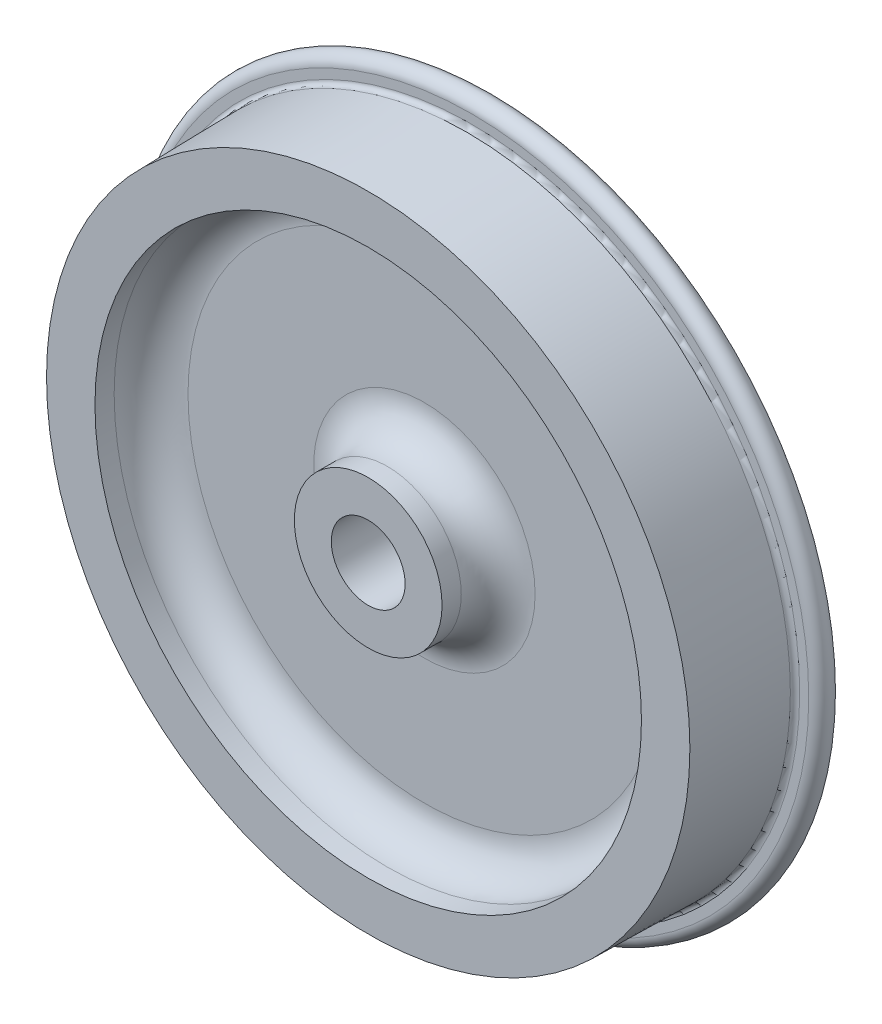
SolidWorks part; units mm, degrees
material "Gray Cast Iron"
ref_plane "Front Plane" through (0, 0, 0) normal (0, 0, 1) x (1, 0, 0)
ref_plane "Top Plane" through (0, 0, 0) normal (0, 1, 0) x (1, 0, 0)
ref_plane "Right Plane" through (0, 0, 0) normal (1, 0, 0) x (0, 0, -1)
sketch "Sketch1" plane through (0, 0, 0) normal (0, 0, 1) x (1, 0, 0)
  circle A0 centre (0, 0) radius 58.42
  dimension "D1" = 116.84
extrude "Boss-Extrude1" add sketch "Sketch1" along normal blind 13.97
sketch "Sketch2" plane through (0, 0, 13.97) normal (0, 0, 1) x (1, 0, 0)
  circle A0 centre (0, 0) radius 12.7
  circle A1 centre (0, 0) radius 46.99
  dimension "D1" = 25.4
  dimension "D2" = 93.98
extrude "Cut-Extrude1" cut sketch "Sketch2" against normal blind 9.652
fillet "Fillet1" radius 6.35 2 edges at (12.7, 0, 4.318) (46.99, 0, 4.318)
sketch "Sketch3" plane through (0, 0, 0) normal (0, 0, -1) x (-1, 0, 0)
  circle A0 centre (0, 0) radius 60.96
  dimension "D1" = 121.92
extrude "Boss-Extrude2" add sketch "Sketch3" along normal blind 7.62
sketch "Sketch4" plane through (0, 0, 13.97) normal (0, 0, 1) x (1, 0, 0)
  circle A0 centre (0, 0) radius 6.35
  dimension "D1" = 12.7
extrude "Cut-Extrude2" cut sketch "Sketch4" against normal through all
sketch "Sketch5" plane through (0, 0, 0) normal (0, 0, 1) x (1, 0, 0)
  circle A0 centre (0, 0) radius 60.96 construction
  circle A1 centre (0, 0) radius 60.96
  circle A2 centre (0, 0) radius 58.42 construction
  circle A3 centre (0, 0) radius 58.42
extrude "FlangeWidthMachined" cut sketch "Sketch5" against normal blind 3.81
sketch "Sketch7" plane through (0, 0, 13.97) normal (0, 0, 1) x (1, 0, 0)
  circle A0 centre (0, 0) radius 58.42 construction
  circle A1 centre (0, 0) radius 58.42
  circle A2 centre (0, 0) radius 55.5625
  dimension "D1" = 111.125
extrude "Cut-Extrude5" cut sketch "Sketch7" against normal up to surface (17.78 mm away) up to face at (58.42, 0, -3.81)
sketch "Sketch6" plane through (0, 0, -3.81) normal (0, 0, 1) x (1, 0, 0)
  circle A1 centre (0, 0) radius 55.5625 construction
  circle A2 centre (0, 0) radius 59.8805
  circle A3 centre (0, 0) radius 60.96 construction
  circle A4 centre (0, 0) radius 60.96
  circle A6 centre (0, 0) radius 55.5625 construction
  dimension "D1" = 4.318
extrude "Flange Depth Machined" cut sketch "Sketch6" against normal through all
draft "Draft1" type of draft neutral plane draft angle 1 neutral plane "Front Plane" faces to draft 1 face at (55.5625, 0, -3.81) neutral plane through (0, 0, 0) neutral plane normal (0, 0, 1) parameters "D1"=1
fillet "Fillet2" radius 0.8128 1 edges at (55.629, 0, -3.81)
fillet "Fillet3" 2 edges at (59.8805, 0, -7.62) (59.8805, 0, -3.81) type full round first side face at (6.35, 0, -7.62) second side face at (56.4277, 0, -3.81) middle face at (59.8805, 0, -7.62)
